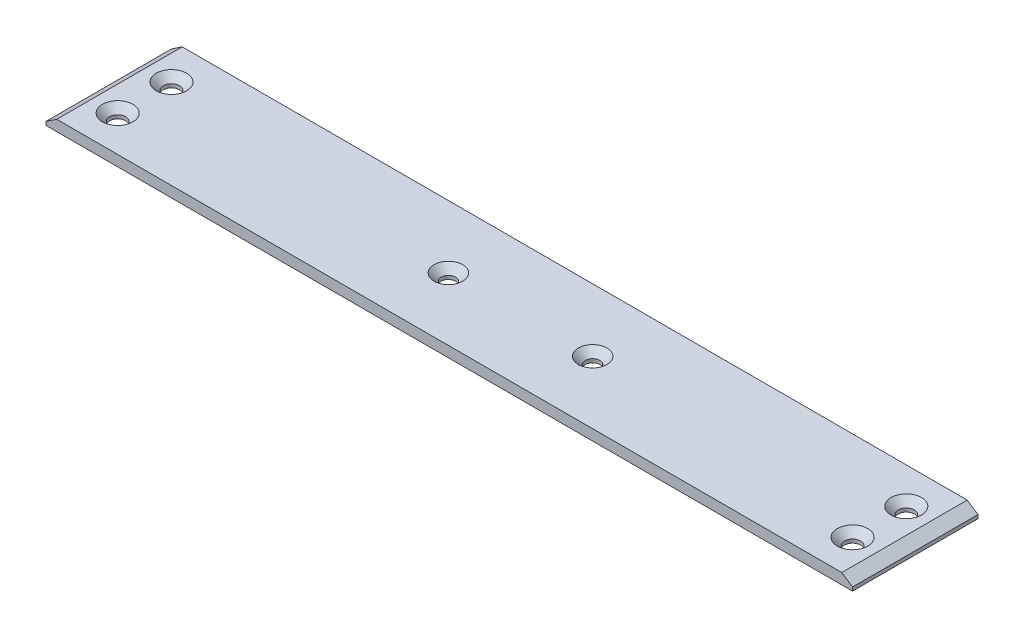
SolidWorks part; units mm, degrees
ref_plane "Front Plane" through (0, 0, 0) normal (0, 0, 1) x (1, 0, 0)
ref_plane "Top Plane" through (0, 0, 0) normal (0, 1, 0) x (1, 0, 0)
ref_plane "Right Plane" through (0, 0, 0) normal (1, 0, 0) x (0, 0, -1)
sketch "Sketch1" plane through (0, 0, 0) normal (0, 1, 0) x (1, 0, 0)
  line L0 (-112.5, 17.5) -> (112.5, -17.5) construction
  line L1 (-112.5, 17.5) -> (112.5, 17.5)
  line L2 (-112.5, 17.5) -> (-112.5, -17.5)
  line L3 (-112.5, -17.5) -> (112.5, -17.5)
  line L4 (112.5, 17.5) -> (112.5, -17.5)
  point P4 (0, 0)
  dimension "D1" = 225
  dimension "D2" = 35
extrude "Boss-Extrude1" add sketch "Sketch1" along normal blind 3
sketch "Sketch3" plane through (0, 3, 0) normal (0, 1, 0) x (1, 0, 0)
  circle A0 centre (-17.75, 0) radius 2
  circle A1 centre (22.5, 0) radius 2
  dimension "D3" = 4
  dimension "D1" = 17.75
  dimension "D2" = 22.5
extrude "Cut-Extrude1" cut sketch "Sketch3" against normal through all both and the other way through all
chamfer "Chamfer1" distance 2 angle 45 2 edges at (22.5, 3, 2) (-17.75, 3, 2)
sketch "Sketch4" plane through (0, 3, 0) normal (0, 1, 0) x (1, 0, 0)
  line L0 (-112.5, 0) -> (-61.6854, 0) construction
  line L1 (-112.5, 17.5) -> (-112.5, -17.5) construction
  circle A0 centre (-102.5, 7.5) radius 2.25
  circle A1 centre (-102.5, -7.5) radius 2.25
  dimension "D1" = 4.5
  dimension "D2" = 15
  dimension "D3" = 10
extrude "Cut-Extrude2" cut sketch "Sketch4" against normal through all both and the other way through all
chamfer "Chamfer2" distance 2 angle 45 2 edges at (-102.5, 3, 9.75) (-102.5, 3, -5.25)
mirror "Mirror1" about plane through (0, 0, 0) normal (1, 0, 0) of "Chamfer2", "Cut-Extrude2"
chamfer "Chamfer3" distance 2 distance2 3 2 edges at (112.5, 3, 0) (-112.5, 3, 0) first distance on face at (112.5, 1.5, 0) first distance on face at (-112.5, 1.5, 0)
